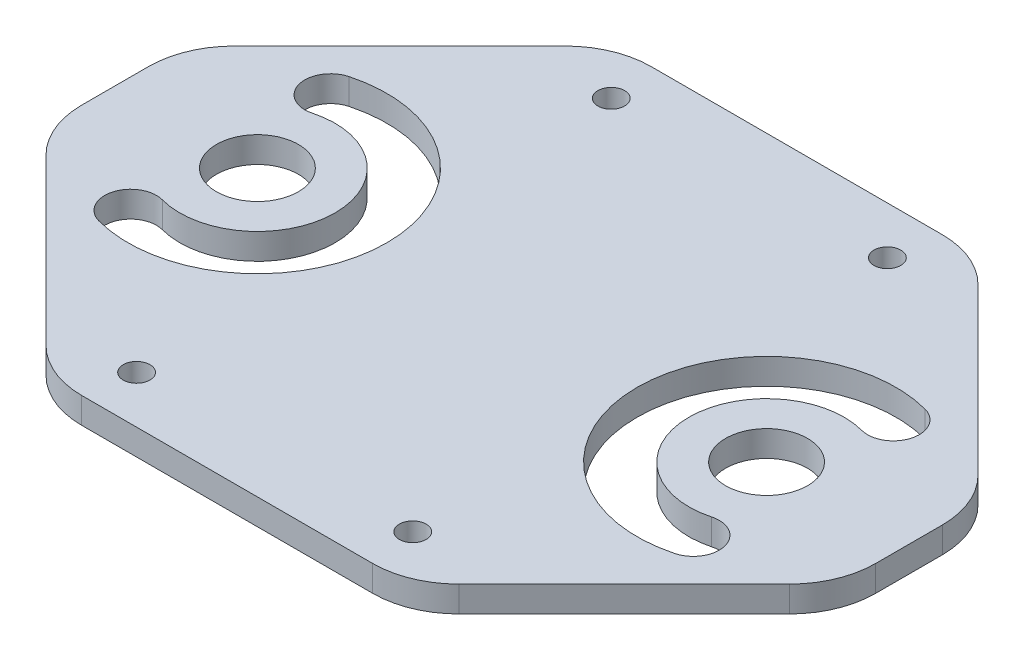
SolidWorks part; units mm, degrees
material "Thornel Mat VMA"
ref_plane "前视基准面" through (0, 0, 0) normal (0, 0, 1) x (1, 0, 0)
ref_plane "上视基准面" through (0, 0, 0) normal (0, 1, 0) x (1, 0, 0)
ref_plane "右视基准面" through (0, 0, 0) normal (1, 0, 0) x (0, 0, -1)
sketch "草图1" plane through (0, 0, 0) normal (0, 1, 0) x (1, 0, 0)
  line L1 (-16, 27.5) -> (16, 27.5) construction
  line L2 (-16, 27.5) -> (-16, -27.5) construction
  line L3 (-16, -27.5) -> (16, -27.5) construction
  line L4 (16, 27.5) -> (16, -27.5) construction
  line L5 (-16, 27.5) -> (16, -27.5) construction
  line L6 (-16, -27.5) -> (16, 27.5) construction
  line L7 (-46, 33) -> (46, 33)
  line L8 (-46, 33) -> (-46, -33)
  line L9 (-46, -33) -> (46, -33)
  line L10 (46, 33) -> (46, -33)
  line L11 (-46, 33) -> (46, -33) construction
  line L12 (-46, -33) -> (46, 33) construction
  circle A0 centre (-16, 27.5) radius 1.55
  circle A1 centre (16, 27.5) radius 1.55
  circle A2 centre (16, -27.5) radius 1.55
  circle A3 centre (-16, -27.5) radius 1.55
  point P0 (0, 0)
  point P10 (0, 0)
  dimension "D3" = 3.1
  dimension "D4" = 3.1
  dimension "D5" = 3.1
  dimension "D6" = 3.1
  dimension "D1" = 55
  dimension "D2" = 32
  dimension "D7" = 66
  dimension "D8" = 92
extrude "凸台-拉伸1" add sketch "草图1" along normal blind 3
chamfer "倒角1" distance 25 angle 45 4 edges at (-46, 1.5, 33) (46, 1.5, 33) (46, 1.5, -33) (-46, 1.5, -33)
sketch "草图3" plane through (0, 3, 0) normal (0, 1, 0) x (1, 0, 0)
  line L0 (0, 0) -> (0, 21.4113) construction
  line L1 (-29.5, 21.3564) -> (-29.5, -21.3564) construction
  line L2 (-29.5, 0) -> (-32.6058, -11.5911) construction
  line L3 (-29.5, 0) -> (-32.6058, 11.5911) construction
  line L4 (29.5, 0) -> (32.6058, 11.5911) construction
  line L5 (29.5, 0) -> (32.6058, -11.5911) construction
  circle A1 centre (-29.5, 0) radius 2.9 construction
  circle A3 centre (-29.5, 0) radius 2.9 construction
  circle A4 centre (-29.5, 0) radius 4.75
  circle A5 centre (29.5, 0) radius 2.9 construction
  circle A6 centre (29.5, 0) radius 4.75
  arc A7 (-32.6058, -11.5911) -> (-32.6058, 11.5911) centre (-29.5, 0) ccw construction
  arc A8 (-33.3823, -14.4889) -> (-33.3823, 14.4889) centre (-29.5, 0) ccw
  arc A9 (-31.8294, -8.6933) -> (-31.8294, 8.6933) centre (-29.5, 0) ccw
  arc A10 (-31.8294, -8.6933) -> (-33.3823, -14.4889) centre (-32.6058, -11.5911) ccw
  arc A11 (-33.3823, 14.4889) -> (-31.8294, 8.6933) centre (-32.6058, 11.5911) ccw
  arc A12 (32.6058, -11.5911) -> (32.6058, 11.5911) centre (29.5, 0) cw construction
  arc A13 (33.3823, -14.4889) -> (33.3823, 14.4889) centre (29.5, 0) cw
  arc A14 (31.8294, -8.6933) -> (31.8294, 8.6933) centre (29.5, 0) cw
  arc A15 (31.8294, -8.6933) -> (33.3823, -14.4889) centre (32.6058, -11.5911) cw
  arc A16 (33.3823, 14.4889) -> (31.8294, 8.6933) centre (32.6058, 11.5911) cw
  circle A17 centre (29.5, 0) radius 2.9 construction
  circle A18 centre (29.5, 0) radius 4.75
  point P12 (-17.5, 0)
  point P20 (-29.5, 0)
  point P25 (17.5, 0)
  dimension "D1" = 9.5
  dimension "D2" = 12
  dimension "D3" = 3
  dimension "D4" = 15
  dimension "D5" = 15
extrude "切除-拉伸1" cut sketch "草图3" against normal through all and the other way through all contours A8 A11 A9 A10 | A4 | A16 A13 A15 A14 | A6 region at (-29.5, 3, 0) region at (29.5, 3, 0) region at (-35.1493, 3, 10.9096) region at (14.8668, 3, 0)
fillet "圆角1" radius 10 8 edges at (21, 1.5, -33) (46, 1.5, -8) (46, 1.5, 8) (21, 1.5, 33) (-21, 1.5, 33) (-46, 1.5, 8) (-46, 1.5, -8) (-21, 1.5, -33)
